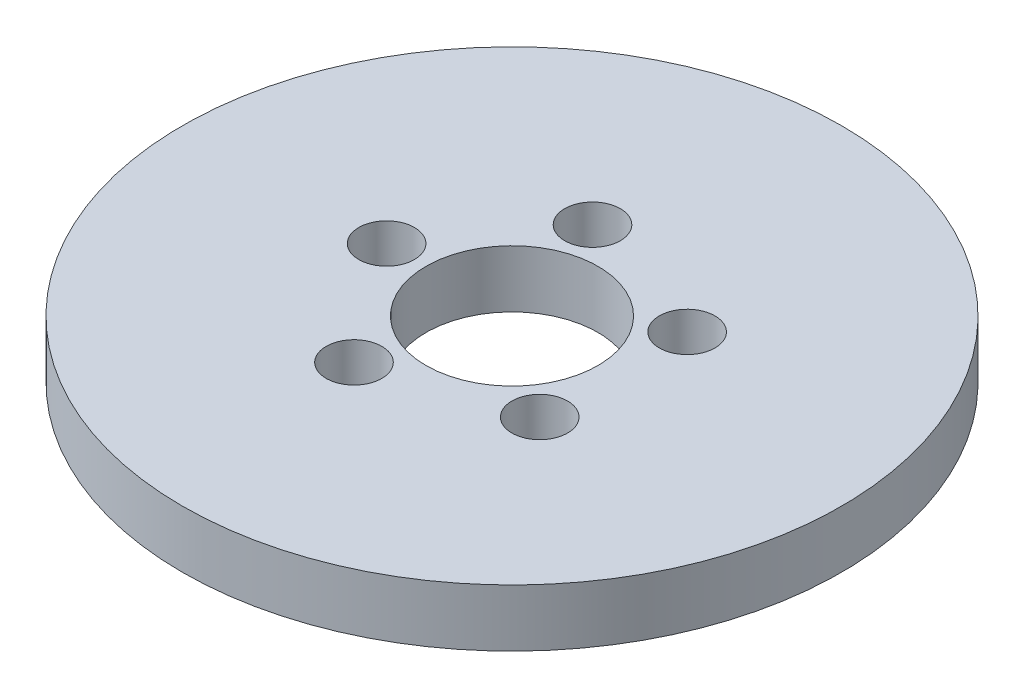
SolidWorks part; units mm, degrees
ref_plane "Front Plane" through (0, 0, 0) normal (0, 0, 1) x (1, 0, 0)
ref_plane "Top Plane" through (0, 0, 0) normal (0, 1, 0) x (1, 0, 0)
ref_plane "Right Plane" through (0, 0, 0) normal (1, 0, 0) x (0, 0, -1)
sketch "Sketch1" plane through (0, 0, 0) normal (0, 1, 0) x (1, 0, 0)
  circle A0 centre (0, 0) radius 57.5
  dimension "FLANGE_OD" = 115
extrude "Boss-Extrude1" add sketch "Sketch1" along normal blind 10
sketch "Sketch2" plane through (0, 0, 0) normal (0, 1, 0) x (1, 0, 0)
  circle A0 centre (0, 0) radius 15
  dimension "BORE_D" = 30
extrude "Cut-Extrude1" cut sketch "Sketch2" along normal through all
sketch "Sketch3" plane through (0, 10, 0) normal (0, 1, 0) x (1, 0, 0)
  circle A0 centre (0, 0) radius 21.8777 construction
  circle A1 centre (-21.8777, 0) radius 4.8532
  dimension "BOLT_D" = 9.7064
  dimension "BOLT_PCD" = 43.7553
extrude "Cut-Extrude2" cut sketch "Sketch3" against normal blind 9.3102
pattern_circular "CirPattern1" count 5 over 360 about axis through (0, 0, 0) along (0, 1, 0) of "Cut-Extrude2"
